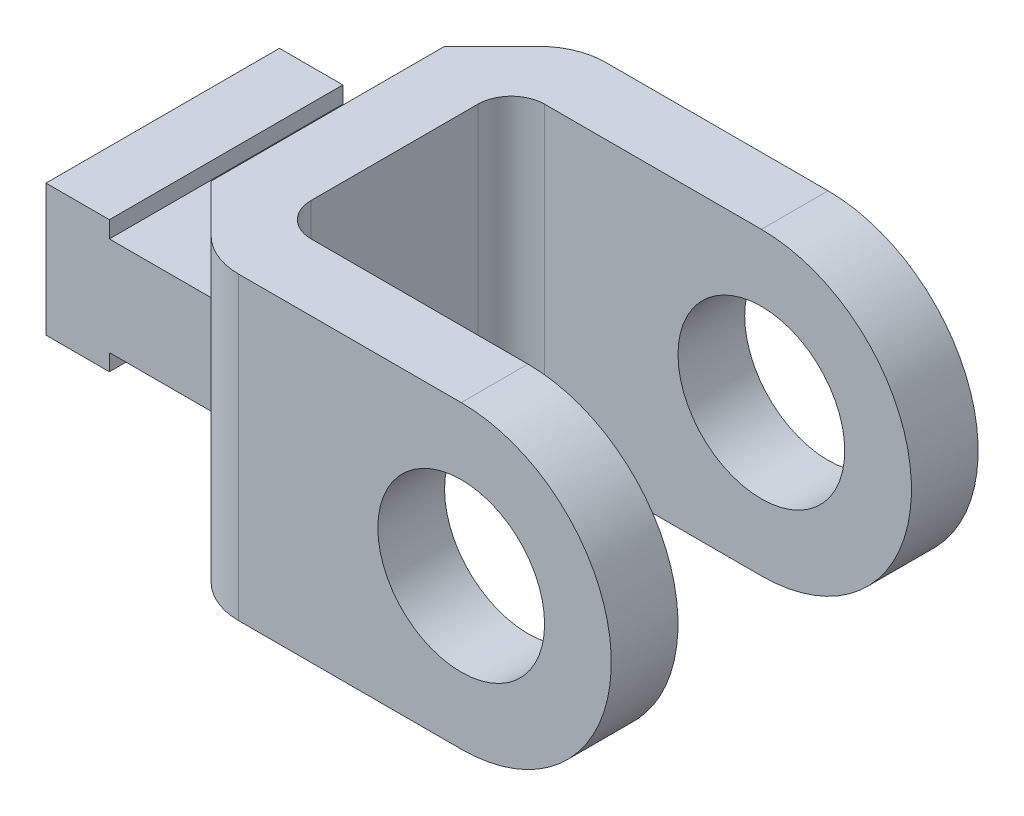
SolidWorks part; units mm, degrees
ref_plane "Front Plane" through (0, 0, 0) normal (0, 0, 1) x (1, 0, 0)
ref_plane "Top Plane" through (0, 0, 0) normal (0, 1, 0) x (1, 0, 0)
ref_plane "Right Plane" through (0, 0, 0) normal (1, 0, 0) x (0, 0, -1)
sketch "Sketch1" plane through (0, 0, 0) normal (0, 0, 1) x (1, 0, 0)
  line L0 (-4.05, 1.475) -> (-4.05, 1.975)
  line L1 (-4.05, -1.475) -> (-1, -1.475)
  line L7 (-1, -4.5) -> (1, -4.5)
  line L8 (-1, -4.5) -> (-1, -1.475)
  line L11 (-7.7473, 0) -> (6.5352, 0) construction
  line L18 (-1, 4.5) -> (1, 4.5)
  line L19 (1, -4.5) -> (1, 4.5)
  line L20 (-1, -4.5) -> (1, 4.5) construction
  line L21 (-1, 4.5) -> (1, -4.5) construction
  line L22 (-4.05, 1.475) -> (-1, 1.475)
  line L24 (-4.05, -1.475) -> (-1, 1.475) construction
  line L25 (-4.05, 1.475) -> (-1, -1.475) construction
  line L26 (-5.95, -1.975) -> (-4.05, -1.975)
  line L27 (-5.95, -1.975) -> (-5.95, 1.975)
  line L28 (-5.95, 1.975) -> (-4.05, 1.975)
  line L29 (-4.05, -1.975) -> (-4.05, -1.475)
  line L30 (-5.95, -1.975) -> (-4.05, 1.975) construction
  line L31 (-5.95, 1.975) -> (-4.05, -1.975) construction
  line L32 (-1, 1.475) -> (-1, 4.5)
  point P0 (0, 0)
  point P3 (-2.525, 0)
  point P5 (0, 0)
  point P12 (-5, 0)
  dimension "D1" = 2
  dimension "D2" = 9
  dimension "D3" = 2.95
  dimension "D4" = 3.05
  dimension "D5" = 3.95
  dimension "D6" = 1.9
extrude "Boss-Extrude2" add sketch "Sketch1" along normal blind 7
sketch "Sketch2" plane through (0, 0, 0) normal (0, 0, 1) x (1, 0, 0)
  line L0 (-1, 4.5) -> (-1, 1.475) construction
  line L1 (-1, 4.5) -> (8.5, 4.5)
  line L2 (-1, 4.5) -> (-1, -4.5)
  line L3 (-1, -4.5) -> (8.5, -4.5)
  arc A0 (8.5, -4.5) -> (8.5, 4.5) centre (8.5, 0) ccw
  circle A1 centre (8.5, 0) radius 2.5
  circle A2 centre (8.5, 0) radius 6.5 construction
  point P1 (13, 0)
  point P11 (2, 0)
  dimension "D3" = 5
  dimension "D2" = 13
  dimension "D1" = 14
extrude "Boss-Extrude3" add sketch "Sketch2" against normal blind 2
ref_plane "Plane1" through (0, 4.5, 0) normal (0, 1, 0) x (1, 0, 0)
sketch "Sketch4" plane through (0, 4.5, 0) normal (0, 1, 0) x (1, 0, 0)
  line L0 (1, -0.5237) -> (1, 2.9724) construction
  line L1 (8.5, 2) -> (-1, 2) construction
  line L2 (-1, 0) -> (1, 2)
  line L3 (1, 2) -> (-1, 2)
  line L4 (-1, 0) -> (-1, 2)
  line L5 (1, -7) -> (1, 0) construction
  point P0 (1, -0.5237)
  point P4 (1, 2)
  point P5 (0, 0)
  point P12 (0, 0)
  point P15 (0, 0)
  point P16 (2.1003, -0.5237)
extrude "Cut-Extrude3" cut sketch "Sketch4" against normal through all
fillet "Fillet1" radius 1 1 edges at (1, 0, 0)
fillet "Fillet2" radius 2 1 edges at (1, 0, -2)
ref_plane "Plane2" through (0, 0, 3.5) normal (0, 0, 1) x (1, 0, 0)
mirror "Mirror2" about plane through (0, 0, 3.5) normal (0, 0, 1) of "Boss-Extrude2", "Fillet2", "Cut-Extrude3", "Boss-Extrude3"
fillet "Fillet3" radius 1 1 edges at (1, 0, 7)
